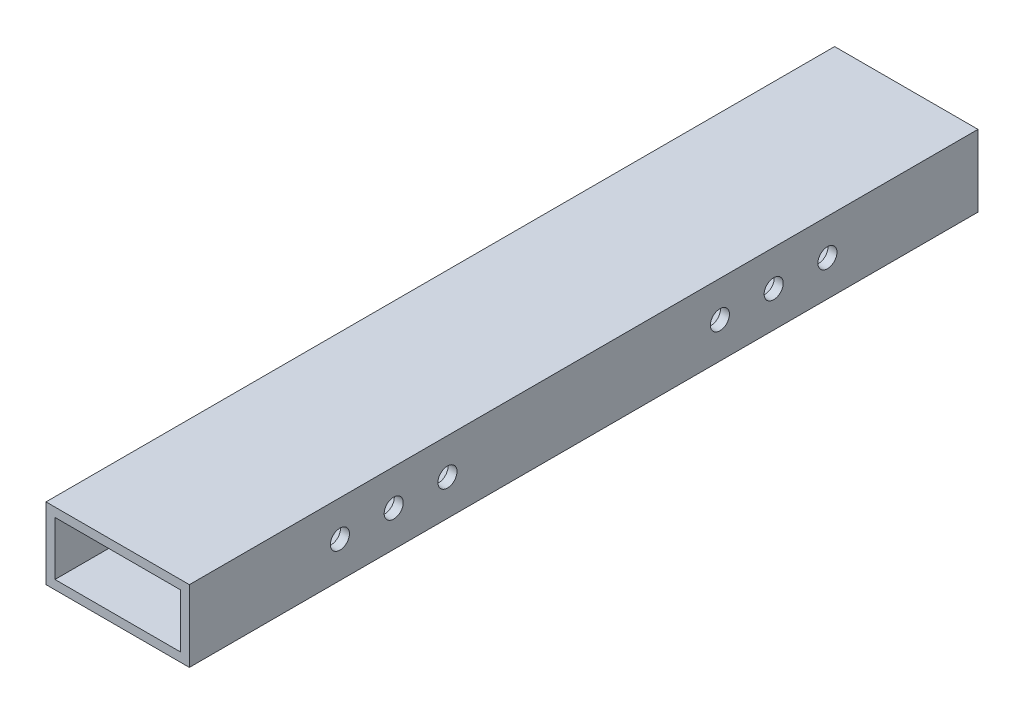
SolidWorks part; units mm, degrees
ref_plane "Front Plane" through (0, 0, 0) normal (0, 0, 1) x (1, 0, 0)
ref_plane "Top Plane" through (0, 0, 0) normal (0, 1, 0) x (1, 0, 0)
ref_plane "Right Plane" through (0, 0, 0) normal (1, 0, 0) x (0, 0, -1)
sketch "Sketch1" plane through (0, 0, 0) normal (0, 0, 1) x (1, 0, 0)
  line L0 (3.175, 22.225) -> (47.625, 22.225)
  line L1 (0, 0) -> (50.8, 0)
  line L2 (0, 0) -> (0, 25.4)
  line L3 (0, 25.4) -> (50.8, 25.4)
  line L4 (50.8, 0) -> (50.8, 25.4)
  line L5 (47.625, 3.175) -> (47.625, 22.225)
  line L6 (3.175, 3.175) -> (47.625, 3.175)
  line L7 (3.175, 3.175) -> (3.175, 22.225)
  dimension "D1" = 25.4
  dimension "D2" = 50.8
  dimension "D3" = 3.175
extrude "Boss-Extrude1" add sketch "Sketch1" along normal blind 279.4
sketch "Sketch2" plane through (50.8, 0, 0) normal (1, 0, 0) x (0, 0, -1)
  line L0 (-279.4, 0) -> (-279.4, 25.4) construction
  line L1 (-139.7, 25.4) -> (-139.7, 0) construction
  line L2 (-279.4, 25.4) -> (0, 25.4) construction
  line L3 (-279.4, 0) -> (0, 0) construction
  circle A0 centre (-226.06, 12.7) radius 3.3782
  circle A1 centre (-187.96, 12.7) radius 3.3782
  circle A2 centre (-207.01, 12.7) radius 3.3782
  circle A3 centre (-91.44, 12.7) radius 3.3782
  circle A4 centre (-53.34, 12.7) radius 3.3782
  circle A5 centre (-72.39, 12.7) radius 3.3782
  dimension "D7" = 6.7564
  dimension "D8" = 6.7564
  dimension "D9" = 6.7564
  dimension "D1" = 53.34
  dimension "D2" = 19.05
  dimension "D3" = 19.05
  dimension "D4" = 12.7
  dimension "D5" = 12.7
  dimension "D6" = 12.7
extrude "Cut-Extrude1" cut sketch "Sketch2" against normal through all
